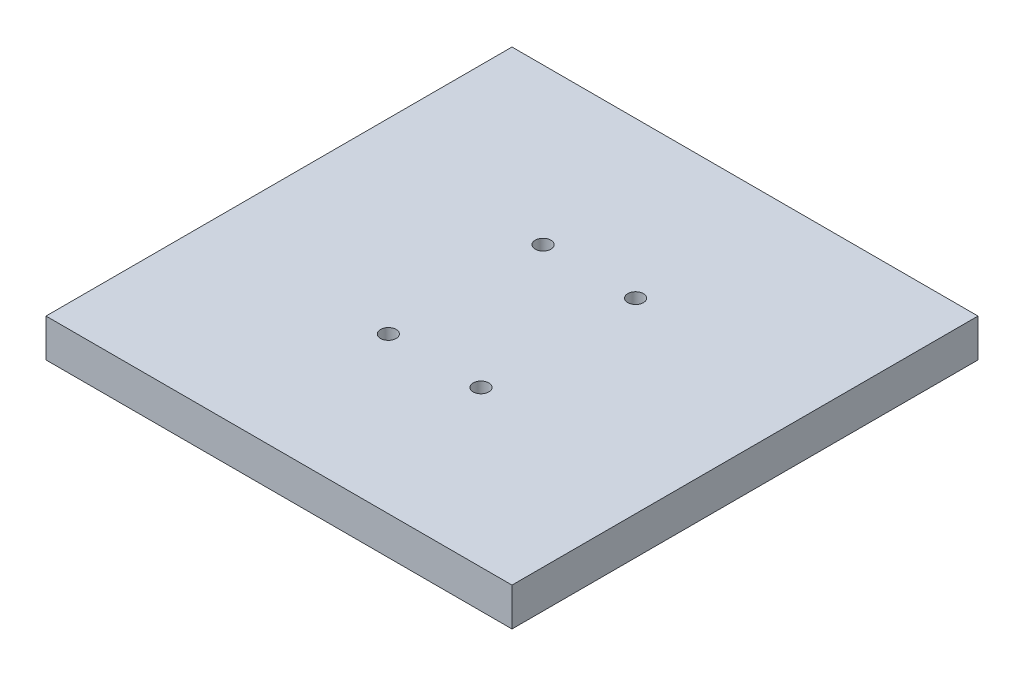
SolidWorks part; units mm, degrees
ref_plane "Front Plane" through (0, 0, 0) normal (0, 0, 1) x (1, 0, 0)
ref_plane "Top Plane" through (0, 0, 0) normal (0, 1, 0) x (1, 0, 0)
ref_plane "Right Plane" through (0, 0, 0) normal (1, 0, 0) x (0, 0, -1)
sketch "Sketch1" plane through (0, 0, 0) normal (0, 1, 0) x (1, 0, 0)
  circle A2 centre (-49, 0) radius 42.5 construction
  circle A3 centre (49, 0) radius 42.5 construction
  circle A4 centre (49, 0) radius 49 construction
  circle A5 centre (-49, 0) radius 49 construction
  dimension "D1" = 85
  dimension "D4" = 98
sketch "Sketch2" plane through (0, 0, 0) normal (0, 1, 0) x (1, 0, 0)
  line L0 (49, -49) -> (-49, -49)
  line L1 (49, -49) -> (49, 49)
  line L2 (-49, -49) -> (-49, 49)
  line L3 (49, 49) -> (-49, 49)
  line L4 (49, -49) -> (-49, 49) construction
  line L5 (-49, -49) -> (49, 49) construction
  point P1 (0, 0)
  dimension "D1" = 98
  dimension "D2" = 98
extrude "Boss-Extrude1" add sketch "Sketch2" against normal blind 8
sketch "Sketch6" plane through (0, 0, 0) normal (0, 1, 0) x (1, 0, 0)
  line L0 (0, 0) -> (-49, 0) construction
  line L1 (0, 0) -> (49, 0) construction
  line L5 (0, -4.4) -> (0, 4.4) construction
  circle A0 centre (-9.7351, -16.264) radius 1.65
  circle A2 centre (-49, 0) radius 42.5 construction
  circle A3 centre (-65.264, -39.2649) radius 1.65 [skipped]
  circle A4 centre (-88.2649, -16.264) radius 1.65 [skipped]
  circle A5 centre (-88.2649, 16.264) radius 1.65 [skipped]
  circle A6 centre (-65.264, 39.2649) radius 1.65 [skipped]
  circle A8 centre (-9.7351, 16.264) radius 1.65
  circle A10 centre (9.7351, 16.264) radius 1.65
  circle A11 centre (9.7351, -16.264) radius 1.65
  circle A13 centre (-32.736, -39.2649) radius 1.65 [skipped]
  circle A14 centre (-32.736, 39.2649) radius 1.65 [skipped]
  point P13 (0, 0)
  dimension "D1" = 3.3
  dimension "D2" = 22.5
  dimension "D4" = 42.5
  dimension "D5" = 22.5
  dimension "D3" = 8
extrude "Cut-Extrude1" cut sketch "Sketch6" against normal up to surface (8 mm away) up to face at (0, -8, 0)
